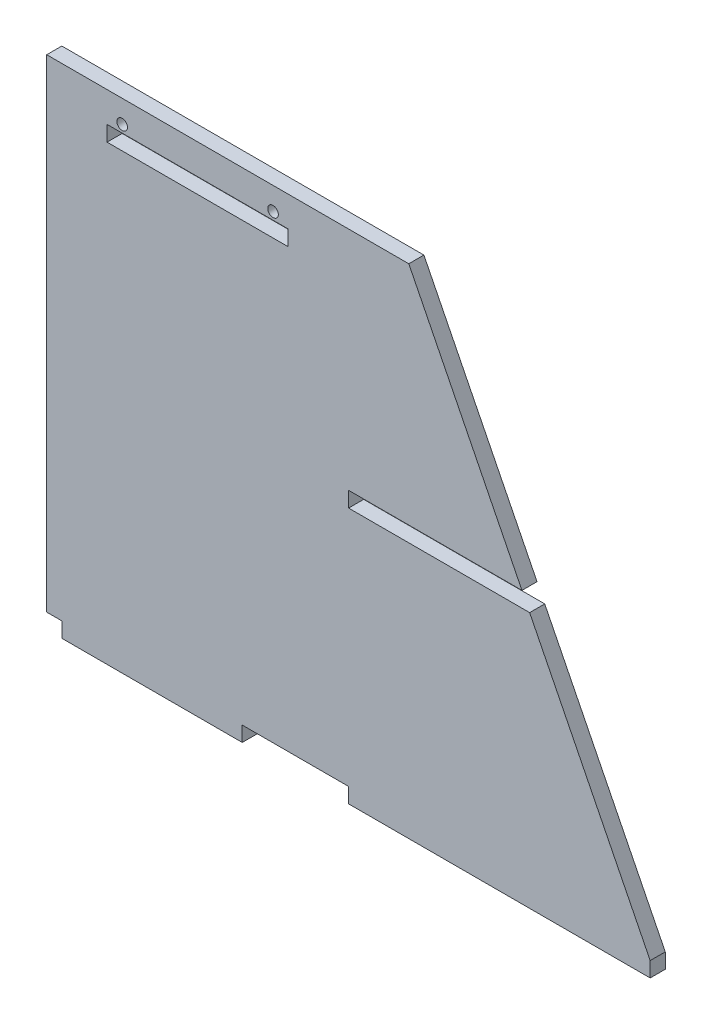
SolidWorks part; units mm, degrees
ref_plane "Front Plane" through (0, 0, 0) normal (0, 0, 1) x (1, 0, 0)
ref_plane "Top Plane" through (0, 0, 0) normal (0, 1, 0) x (1, 0, 0)
ref_plane "Right Plane" through (0, 0, 0) normal (1, 0, 0) x (0, 0, -1)
sketch "Sketch1" plane through (0, 0, 0) normal (0, 0, 1) x (1, 0, 0)
  line L0 (0, 0) -> (200, 0)
  line L5 (0, 0) -> (0, 160)
  line L6 (5, 0) -> (64.8, 0)
  line L7 (5, 0) -> (5, -5)
  line L8 (5, -5) -> (64.8, -5)
  line L9 (64.8, 0) -> (64.8, -5)
  line L10 (200, 0) -> (100, 0)
  line L11 (200, 0) -> (200, -5)
  line L12 (200, -5) -> (100, -5)
  line L13 (100, 0) -> (100, -5)
  line L14 (0, 160) -> (120, 160)
  line L15 (120, 160) -> (200, 0)
  dimension "D1" = 59.8
  dimension "D2" = 5
  dimension "D3" = 5
  dimension "D4" = 100
  dimension "D5" = 200
  dimension "D6" = 160
  dimension "D7" = 120
extrude "Boss-Extrude1" add sketch "Sketch1" along normal blind 5 contours L15 L14 L5 L0 | L0 L13 L12 L11 | L8 L9 L6 L7 region at (81.6667, 73.3333, 0) region at (150, -2.5, 0)
sketch "Sketch2" plane through (0, 0, 5) normal (0, 0, 1) x (1, 0, 0)
  line L0 (0, 0) -> (0, 160) construction
  line L1 (20, 150) -> (80, 150)
  line L2 (20, 150) -> (20, 144.9)
  line L3 (20, 144.9) -> (80, 144.9)
  line L4 (80, 150) -> (80, 144.9)
  line L5 (0, 160) -> (120, 160) construction
  dimension "D1" = 5.1
  dimension "D2" = 60
  dimension "D3" = 20
  dimension "D4" = 10
extrude "Cut-Extrude1" cut sketch "Sketch2" against normal blind 5
sketch "Sketch3" plane through (0, 0, 5) normal (0, 0, 1) x (1, 0, 0)
  line L0 (80, 150) -> (20, 150) construction
  line L1 (0, 0) -> (0, 160) construction
  line L2 (50, -850) -> (50, 49150) construction
  circle A0 centre (25, 152.5) radius 1.75
  circle A1 centre (75, 152.5) radius 1.75
  point P10 (50, 150)
  dimension "D1" = 3.5
  dimension "D3" = 25
  dimension "D2" = 2.5
extrude "Cut-Extrude2" cut sketch "Sketch3" against normal blind 5
sketch "Sketch4" plane through (0, 0, 5) normal (0, 0, 1) x (1, 0, 0)
  line L0 (120, 160) -> (200, 0) construction
  line L1 (160.05, 79.9) -> (100.05, 79.9)
  line L2 (160.05, 79.9) -> (160.05, 85)
  line L3 (160.05, 85) -> (100.05, 85)
  line L4 (100.05, 79.9) -> (100.05, 85)
  line L5 (200, -5) -> (100, -5) construction
  dimension "D1" = 5.1
  dimension "D2" = 60
  dimension "D3" = 90
extrude "Cut-Extrude3" cut sketch "Sketch4" against normal blind 5
